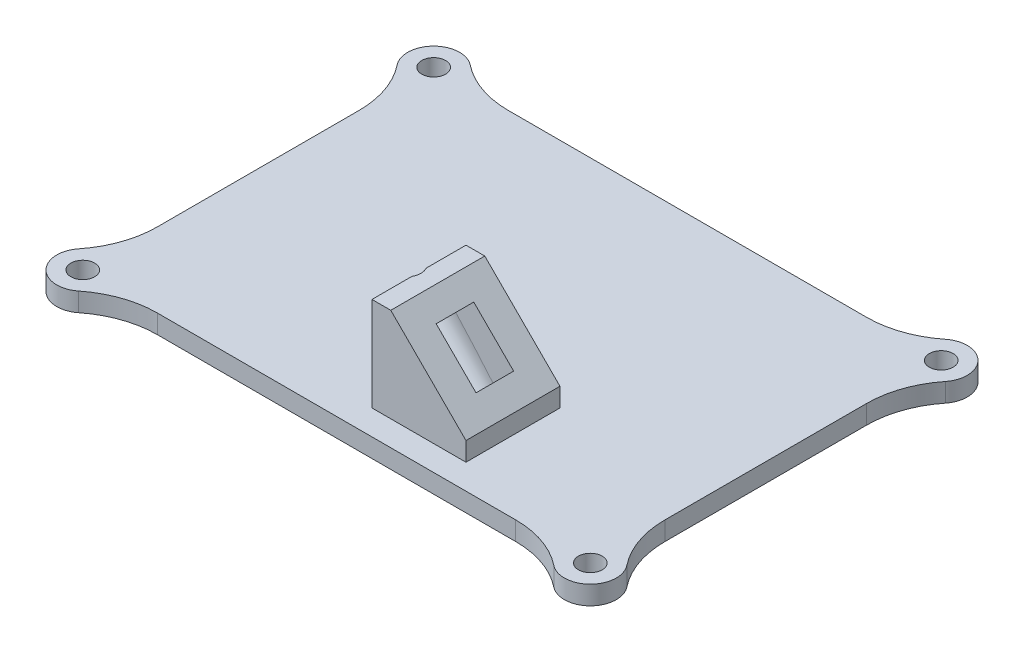
SolidWorks part; units mm, degrees
ref_plane "Front Plane" through (0, 0, 0) normal (0, 0, 1) x (1, 0, 0)
ref_plane "Top Plane" through (0, 0, 0) normal (0, 1, 0) x (1, 0, 0)
ref_plane "Right Plane" through (0, 0, 0) normal (1, 0, 0) x (0, 0, -1)
sketch "Sketch1" plane through (0, 0, 0) normal (0, 1, 0) x (1, 0, 0)
  line L1 (0, 0) -> (81, 0)
  line L2 (0, 0) -> (0, 56)
  line L3 (0, 56) -> (81, 56)
  line L4 (81, 0) -> (81, 56)
  circle A0 centre (81, 0) radius 4.15
  circle A1 centre (81, 56) radius 4.15
  circle A2 centre (0, 56) radius 4.15
  circle A3 centre (0, 0) radius 4.15
  dimension "D3" = 8.3
  dimension "D1" = 81
  dimension "D2" = 56
extrude "Boss-Extrude1" add sketch "Sketch1" along normal blind 3 contours A3 L1 A0 L4 A1 L3 A2 L2 | L3 A1 L4 | L4 A1 L3 | L4 A0 L1 | L1 A0 L4 | L2 A3 L1 | L1 A3 L2 | L3 A2 L2 | L2 A2 L3 region at (1.7613, 0, -1.7613) region at (-0.5871, 0, 0.5871) region at (40.5, 0, -28) region at (79.2387, 0, -1.7613) region at (81.5871, 0, 0.5871) region at (-0.5871, 0, -56.5871) region at (1.7613, 0, -54.2387) region at (79.2387, 0, -54.2387) region at (81.5871, 0, -56.5871)
fillet "Fillet1" radius 15 8 edges at (0, 1.5, -51.85) (4.15, 1.5, -56) (76.85, 1.5, -56) (81, 1.5, -51.85) (81, 1.5, -4.15) (76.85, 1.5, 0) (0, 1.5, -4.15) (4.15, 1.5, 0)
sketch "Sketch2" plane through (0, 3, 0) normal (0, 1, 0) x (1, 0, 0)
  circle A0 centre (0, 56) radius 1.9
  circle A1 centre (81, 56) radius 1.9
  circle A2 centre (81, 0) radius 1.9
  circle A3 centre (0, 0) radius 1.9
  dimension "D1" = 3.8
extrude "Cut-Extrude1" cut sketch "Sketch2" against normal blind 3
sketch "Sketch3" plane through (0, 3, 0) normal (0, 1, 0) x (1, 0, 0)
  line L0 (11.9047, 56) -> (69.0953, 56) construction
  line L1 (3, 3) -> (78, 3)
  line L2 (3, 3) -> (3, 53)
  line L3 (3, 53) -> (78, 53)
  line L4 (78, 3) -> (78, 53)
  line L5 (81, 11.9047) -> (81, 44.0953) construction
  line L7 (42.1545, 4) -> (57.1545, 4)
  line L8 (42.1545, 4) -> (42.1545, 19)
  line L9 (42.1545, 19) -> (57.1545, 19)
  line L10 (57.1545, 4) -> (57.1545, 19)
  point P6 (40.5, 56)
  point P7 (40.5, 53)
  point P10 (81, 28)
  point P11 (78, 28)
  point P16 (0, 0)
  point P17 (0, 0)
  point P18 (0, 0)
  point P19 (0, 0)
  dimension "D1" = 75
  dimension "D2" = 50
  dimension "D3" = 15
  dimension "D4" = 15
  dimension "D5" = 1
extrude "Boss-Extrude2" add sketch "Sketch3" along normal blind 15 contours L8 L7 L10 L9
chamfer "Chamfer1" distance 12 angle 45 1 edges at (57.1545, 18, -11.5)
sketch3d "3DSketch1"
  line L1 (42.1545, 18, -19) -> (42.1545, 18, -4)
  line L2 (42.1545, 18, -4) -> (42.1545, 3, -4) construction
  line L3 (42.1545, 18, -4) -> (42.1545, 18, -19) construction
  circle A0 centre (42.1545, 13.7014, -11.5) radius 3.25
  point P2 (44.4526, 11.4033, -11.5)
  point P10 (42.1545, 18, -11.5)
  dimension "D2" = 6.5
  dimension "D1" = 135
extrude "Cut-Extrude2" cut sketch "3DSketch1" along direction (-0.7071, 0.7071, 0) on the side of the normal blind 12 draft 1 and the other way blind 12 contours A0
sketch "Sketch4" plane through (31.5772, 31.5772, 0) normal (0.7071, 0.7071, 0) x (0, 0, -1)
  line L1 (8.5, -32.0798) -> (14.5, -32.0798)
  line L2 (8.5, -32.0798) -> (8.5, -23.0798)
  line L3 (8.5, -23.0798) -> (14.5, -23.0798)
  line L4 (14.5, -32.0798) -> (14.5, -23.0798)
  line L5 (4, -17.0798) -> (10.3495, -17.0798) construction
  line L6 (4, -17.0798) -> (10.3495, -17.0798)
  line L7 (4, -19.2011) -> (19, -19.2011) construction
  point P6 (11.5, -32.0798)
  point P10 (11.5, -19.2011)
  point P11 (11.5, -23.0798)
  dimension "D1" = 6
  dimension "D2" = 15
  dimension "D3" = 9
extrude "Cut-Extrude3" cut sketch "Sketch4" against normal blind 5 contours L1 L4 L3 L2 region at (51.0791, 12.0754, -11.5)
